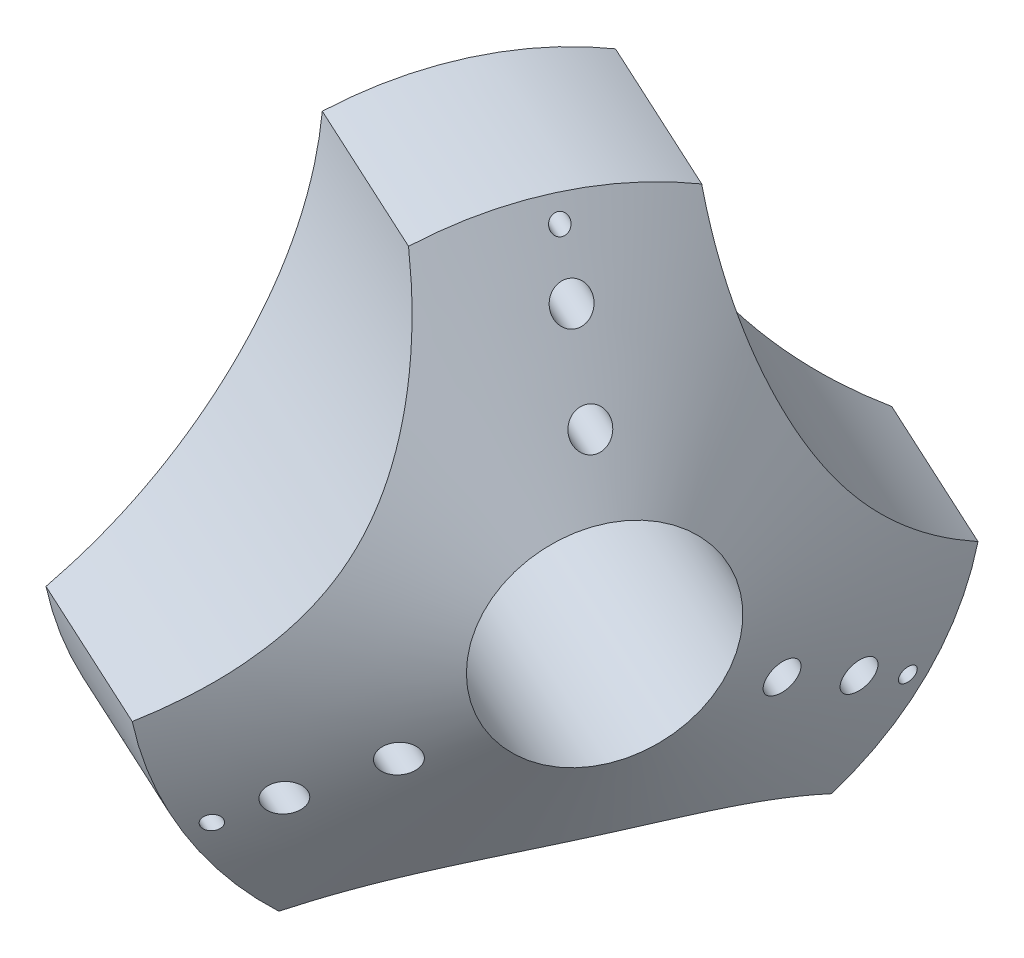
SolidWorks part; units mm, degrees
material "ABS"
ref_plane "前视基准面" through (0, 0, 0) normal (0, 0, 1) x (1, 0, 0)
ref_plane "上视基准面" through (0, 0, 0) normal (0, 1, 0) x (1, 0, 0)
ref_plane "右视基准面" through (0, 0, 0) normal (1, 0, 0) x (0, 0, -1)
other "Configuration Table"
sketch "草图1" plane through (0, 0, 0) normal (0, 1, 0) x (1, 0, 0)
  line L0 (0, 0) -> (50000, 0) construction
  line L1 (0, 0) -> (43301.2702, 25000) construction
  line L2 (0, 0) -> (25000, 43301.2702) construction
  line L3 (0, 0) -> (0, 50000) construction
  line L4 (0, 0) -> (-25000, 43301.2702) construction
  line L5 (0, 0) -> (-43301.2702, 25000) construction
  line L6 (0, -42.1452) -> (-19.2134, -33.2787)
  line L7 (-19.2134, -33.2787) -> (-38.709, -67.046)
  line L8 (-38.709, -67.046) -> (0, -84.9092)
  line L9 (0, -84.9092) -> (0, -42.1452)
  line L10 (-21.968, -74.7716) -> (-17.7779, -65.6918) construction
  line L11 (-17.7779, -65.6918) -> (0, -73.8958)
  line L12 (-17.7779, -65.6918) -> (-33.6882, -58.3496)
  spline S0 degree 4 poles (4.5441, -13.9852) (5.069, -13.9115) (6.1118, -13.7144) (7.5966, -13.2868) (9.4525, -12.4738) (11.1485, -11.4611) (12.673, -10.2854) (14.0902, -8.9027) (15.2006, -7.528) (16.0517, -6.2294) (16.6357, -5.1571) (16.9969, -4.4036) (17.2795, -3.7437) (17.4701, -3.2541) (17.647, -2.7595) (17.7869, -2.3315) (17.8956, -1.9726) (17.9965, -1.6106) (18.0724, -1.3201) (18.1431, -1.0312) (18.201, -0.7763) (18.2495, -0.5466) (18.2961, -0.3139) (18.338, -0.0934) (18.3688, 0.0809) (18.404, 0.2961) (18.438, 0.517) (18.4698, 0.7375) (18.5019, 0.9839) (18.5336, 1.2626) (18.5616, 1.5443) (18.5855, 1.8273) (18.6051, 2.1103) (18.6204, 2.3933) (18.6344, 2.7473) (18.6427, 3.1726) (18.6402, 3.6687) (18.606, 4.6606) (18.4743, 6.0736) (18.1443, 7.891) (17.4882, 10.0676) (16.5951, 12.1579) (15.4804, 14.1385) (14.1536, 15.9992) (12.6297, 17.7192) (10.7951, 19.3989) (8.6272, 20.9716) (6.1287, 22.3558) (3.3088, 23.4722) (0.3713, 24.2251) (-2.6362, 24.611) (-5.6679, 24.6319) (-8.6804, 24.2953) (-11.6337, 23.6131) (-14.4905, 22.6011) (-17.8988, 20.9477) (-21.6682, 18.3857) (-25.4815, 14.66) (-28.8831, 9.6089) (-31.2279, 3.9916) (-32.5355, -2.3024) (-32.5832, -9.4982) (-30.886, -17.2942) (-27.0418, -25.1548) (-21.1423, -32.1629) (-13.78, -37.6027) (-5.394, -41.2569) (3.5764, -43.0207) (12.7127, -42.8868) (21.6333, -40.9289) (30.0036, -37.2857) (37.5425, -32.1439) (44.0239, -25.7248) (49.277, -18.2707) (53.1837, -10.0336) (55.6749, -1.2666) (56.7255, 7.7843) (56.3496, 16.8863) (54.5948, 25.8236) (51.5367, 34.4007) (47.2736, 42.4454) (41.6252, 50.2164) (33.2939, 58.6988) (21.6024, 66.7973) (6.2316, 72.9489) (-11.9297, 75.3897) (-30.1426, 73.5037) (-47.4501, 67.5662) (-63.0493, 58.0235) (-76.3038, 45.4399) (-86.7456, 30.4509) (-94.067, 13.7235) (-98.1075, -4.0757) (-98.837, -22.3066) (-96.337, -40.374) (-90.7813, -57.741) (-82.4178, -73.9383) (-71.5503, -88.568) (-58.5225, -101.306) (-43.7037, -111.9004) (-27.476, -120.169) (-10.2235, -125.9948) (7.6766, -129.3207) (25.8616, -130.1437) (43.989, -128.5088) (59.522, -125.003) (72.4202, -120.5917) (82.8104, -116.0253) (90.8771, -111.8583) (98.6697, -107.1992) (106.1617, -102.071) (114.2246, -95.801) (122.6763, -88.2215) (131.2888, -79.1727) (139.0767, -69.4058) (144.8157, -60.9536) (149.48, -53.1674) (153.2371, -46.1706) (156.1751, -40.0285) (158.8259, -33.7588) (160.8418, -28.4576) (162.3378, -24.1741) (163.5443, -20.3917) (164.5049, -17.1274) (165.2564, -14.393) (165.828, -12.1982) (166.3703, -9.9944) (166.8184, -8.0627) (167.1848, -6.398) (167.4765, -5.0161) (167.7053, -3.8925) (167.892, -2.9476) (168.0629, -2.0497) (168.1956, -1.3461) (168.4043, -0.1916) (168.4882, 0.2863) (168.6688, 1.3366) (168.7622, 1.9047) (168.8711, 2.5704) (169.0198, 3.5044) (169.1948, 4.6573) (169.389, 6.0027) (169.5701, 7.3351) (169.7422, 8.6768) (169.9433, 10.3507) (170.1641, 12.3645) (170.391, 14.7154) (170.6086, 17.4069) (170.7844, 20.1009) (170.9186, 22.7976) (171.0111, 25.4959) (171.0621, 28.1953) (171.0718, 30.8952) (171.0401, 33.595) (170.9491, 36.9686) (170.6302, 43.7113) (169.6923, 53.7988) (167.722, 65.8035) (165.138, 76.2991) (163.208, 82.7681) (162.3863, 85.3398) knots 0 0 0 0 0 0.002183 0.004365 0.006343 0.00832 0.010298 0.012275 0.014479 0.01558 0.016682 0.0173 0.017918 0.018536 0.018845 0.019463 0.019772 0.020081 0.02039 0.020699 0.021008 0.021162 0.021317 0.021626 0.021918 0.022064 0.02221 0.022501 0.022793 0.023085 0.023377 0.023669 0.023961 0.024253 0.024544 0.025128 0.025712 0.026296 0.028631 0.030966 0.033302 0.035637 0.037972 0.040307 0.042695 0.045083 0.048197 0.05131 0.054424 0.057538 0.060652 0.063766 0.066879 0.069993 0.073107 0.07622 0.082448 0.088676 0.094903 0.10113 0.107357 0.114993 0.124334 0.133675 0.143016 0.152357 0.161699 0.17104 0.18038 0.189722 0.199063 0.208404 0.217745 0.227086 0.236427 0.245769 0.25511 0.264451 0.273792 0.283133 0.292474 0.301815 0.313225 0.331907 0.35059 0.369272 0.387954 0.406636 0.425318 0.444001 0.462683 0.481365 0.500047 0.518729 0.537412 0.556094 0.574776 0.593458 0.612141 0.630823 0.649505 0.668187 0.68687 0.705552 0.724234 0.742916 0.752258 0.761599 0.77094 0.780281 0.789622 0.798963 0.812975 0.826987 0.840998 0.85034 0.85501 0.864351 0.873692 0.878363 0.883033 0.887704 0.892374 0.89471 0.897045 0.89938 0.901716 0.904051 0.905219 0.906387 0.907554 0.908722 0.909306 0.90989 0.911057 0.912447 0.912794 0.913142 0.913837 0.915226 0.916616 0.918006 0.919396 0.920785 0.922175 0.924955 0.927734 0.930513 0.933293 0.936072 0.938852 0.941631 0.944411 0.94719 0.94997 0.955529 0.972205 0.988882 1 1 1 1 1 construction
  spline S1 degree 4 poles (18.3541, 0) (18.3651, 0.0621) (18.381, 0.1554) (18.404, 0.2961) (18.438, 0.517) (18.4698, 0.7375) (18.5019, 0.9839) (18.5336, 1.2626) (18.5616, 1.5443) (18.5855, 1.8273) (18.6051, 2.1103) (18.6204, 2.3933) (18.6344, 2.7473) (18.6427, 3.1726) (18.6402, 3.6687) (18.606, 4.6606) (18.4743, 6.0736) (18.1443, 7.891) (17.4882, 10.0676) (16.5951, 12.1579) (15.4804, 14.1385) (14.1536, 15.9992) (12.6297, 17.7192) (10.7951, 19.3989) (8.6272, 20.9716) (6.1287, 22.3558) (3.3088, 23.4722) (0.3713, 24.2251) (-2.6362, 24.611) (-5.6679, 24.6319) (-8.6804, 24.2953) (-11.6337, 23.6131) (-14.4905, 22.6011) (-17.8988, 20.9477) (-21.6682, 18.3857) (-25.4815, 14.66) (-28.8831, 9.6089) (-31.2279, 3.9916) (-32.5355, -2.3024) (-32.5832, -9.4982) (-30.886, -17.2942) (-27.0418, -25.1548) (-21.1423, -32.1629) (-13.78, -37.6027) (-5.394, -41.2569) (3.5764, -43.0207) (12.7127, -42.8868) (21.6333, -40.9289) (30.0036, -37.2857) (37.5425, -32.1439) (44.0239, -25.7248) (49.277, -18.2707) (53.1837, -10.0336) (55.6749, -1.2666) (56.7255, 7.7843) (56.3496, 16.8863) (54.5948, 25.8236) (51.5367, 34.4007) (47.2736, 42.4454) (41.6252, 50.2164) (33.2939, 58.6988) (21.6024, 66.7973) (6.2316, 72.9489) (-11.9297, 75.3897) (-30.1426, 73.5037) (-47.4501, 67.5662) (-63.0493, 58.0235) (-76.3038, 45.4399) (-86.7456, 30.4509) (-94.067, 13.7235) (-98.1075, -4.0757) (-98.837, -22.3066) (-96.337, -40.374) (-90.7813, -57.741) (-82.4178, -73.9383) (-71.5503, -88.568) (-58.5225, -101.306) (-43.7037, -111.9004) (-27.476, -120.169) (-10.2235, -125.9948) (7.6766, -129.3207) (25.8616, -130.1437) (43.989, -128.5088) (59.522, -125.003) (72.4202, -120.5917) (82.8104, -116.0253) (90.8771, -111.8583) (98.6697, -107.1992) (106.1617, -102.071) (114.2246, -95.801) (122.6763, -88.2215) (131.2888, -79.1727) (139.0767, -69.4058) (144.8157, -60.9536) (149.48, -53.1674) (153.2371, -46.1706) (156.1751, -40.0285) (158.8259, -33.7588) (160.8418, -28.4576) (162.3378, -24.1741) (163.5443, -20.3917) (164.5049, -17.1274) (165.2564, -14.393) (165.828, -12.1982) (166.3703, -9.9944) (166.8184, -8.0627) (167.1848, -6.398) (167.4765, -5.0161) (167.7053, -3.8925) (167.892, -2.9476) (168.0629, -2.0497) (168.1956, -1.3461) (168.3264, -0.6223) (168.3933, -0.2484) (168.4372, 0) knots 0.021626 0.021626 0.021626 0.021626 0.021626 0.021918 0.022064 0.02221 0.022501 0.022793 0.023085 0.023377 0.023669 0.023961 0.024253 0.024544 0.025128 0.025712 0.026296 0.028631 0.030966 0.033302 0.035637 0.037972 0.040307 0.042695 0.045083 0.048197 0.05131 0.054424 0.057538 0.060652 0.063766 0.066879 0.069993 0.073107 0.07622 0.082448 0.088676 0.094903 0.10113 0.107357 0.114993 0.124334 0.133675 0.143016 0.152357 0.161699 0.17104 0.18038 0.189722 0.199063 0.208404 0.217745 0.227086 0.236427 0.245769 0.25511 0.264451 0.273792 0.283133 0.292474 0.301815 0.313225 0.331907 0.35059 0.369272 0.387954 0.406636 0.425318 0.444001 0.462683 0.481365 0.500047 0.518729 0.537412 0.556094 0.574776 0.593458 0.612141 0.630823 0.649505 0.668187 0.68687 0.705552 0.724234 0.742916 0.752258 0.761599 0.77094 0.780281 0.789622 0.798963 0.812975 0.826987 0.840998 0.85034 0.85501 0.864351 0.873692 0.878363 0.883033 0.887704 0.892374 0.89471 0.897045 0.89938 0.901716 0.904051 0.905219 0.906387 0.907554 0.908722 0.909306 0.90989 0.911057 0.911057 0.911057 0.911057 0.911057
  spline S2 degree 4 poles (26.7771, -19.4547) (27.2791, -18.9699) (28.2564, -17.9726) (29.6389, -16.3972) (31.5138, -13.8737) (32.9647, -11.4834) (34.0651, -9.2997) (34.8847, -7.3726) (35.3191, -6.2309) (35.6599, -5.2409) (35.9229, -4.4091) (36.0959, -3.8235) (36.2363, -3.3192) (36.3702, -2.8132) (36.4765, -2.3905) (36.5777, -1.9654) (36.6735, -1.5395) (36.7371, -1.2443) (36.7899, -0.9895) (36.8338, -0.7701) (36.8689, -0.5895) (36.9122, -0.3614) (36.9643, -0.079) (37.0022, 0.137) (37.056, 0.4587) (37.1012, 0.7414) (37.1347, 0.96) (37.1737, 1.2255) (37.2176, 1.5413) (37.2661, 1.9157) (37.3168, 2.3441) (37.3624, 2.7721) (37.4134, 3.3079) (37.4649, 3.9519) (37.524, 4.9191) (37.5642, 6.2107) (37.5499, 8.58) (37.2749, 12.0191) (36.4953, 16.2666) (34.9181, 21.2024) (32.7382, 25.9024) (30.2297, 29.9345) (27.5748, 33.3344) (24.3272, 36.7897) (20.4102, 40.1789) (15.3713, 43.5302) (9.113, 46.471) (2.4988, 48.4837) (-3.4771, 49.4179) (-8.6498, 49.6296) (-15.5372, 49.2939) (-22.3494, 48.0444) (-29.7217, 45.4984) (-37.3047, 41.3681) (-42.9225, 37.3494) (-49.2948, 31.5248) (-55.7813, 23.4083) (-61.4472, 12.6507) (-65.4181, -1.9048) (-66.0143, -20.496) (-61.2011, -38.6277) (-51.6663, -54.6681) (-39.5267, -67.0168) (-28.241, -75.0457) (-15.7631, -81.0448) (-2.4709, -84.9081) (11.2641, -86.5959) (25.0917, -86.1269) (38.6859, -83.5703) (51.7521, -79.0376) (62.4941, -73.4702) (71.0671, -67.6624) (77.7289, -62.1925) (82.7475, -57.4634) (87.4361, -52.4071) (91.7776, -47.05) (95.7571, -41.4188) (99.3618, -35.5409) (102.1786, -30.2056) (104.3465, -25.5122) (105.8226, -21.9278) (106.7439, -19.5134) (107.4694, -17.486) (108.0246, -15.8552) (108.5543, -14.216) (109.0585, -12.5687) (109.5372, -10.914) (109.9904, -9.2519) (110.418, -7.5833) (110.7697, -6.1172) (111.0551, -4.8577) (111.2824, -3.8044) (111.4574, -2.9629) (111.6056, -2.2213) (111.7181, -1.6396) (111.7961, -1.2276) (111.8764, -0.7956) (111.9824, -0.2107) (112.0406, 0.1173) (112.149, 0.7476) (112.2197, 1.1704) (112.2736, 1.499) (112.3401, 1.912) (112.4454, 2.5814) (112.5829, 3.4978) (112.7468, 4.6683) (112.9181, 6.007) (113.1127, 7.6834) (113.3147, 9.6981) (113.5046, 12.0531) (113.6588, 14.7487) (113.7504, 17.4473) (113.7796, 20.1472) (113.7303, 24.197) (113.4243, 30.2662) (112.8255, 35.6383) (112.057, 40.3021) (111.5392, 42.9519) knots 0 0 0 0 0 0.005611 0.011222 0.016833 0.02525 0.028055 0.030861 0.033666 0.035069 0.036472 0.037875 0.038576 0.039277 0.04068 0.041381 0.042083 0.042784 0.043135 0.043486 0.043836 0.044187 0.044888 0.045754 0.046187 0.04662 0.047052 0.047485 0.048351 0.049216 0.050082 0.050948 0.051813 0.053545 0.055276 0.058738 0.062201 0.072588 0.082976 0.093363 0.103751 0.114138 0.121063 0.127988 0.141838 0.155688 0.169538 0.183388 0.197238 0.204163 0.211088 0.238788 0.252638 0.266488 0.280339 0.294189 0.321888 0.349589 0.377289 0.414571 0.469971 0.497671 0.525371 0.553071 0.580771 0.608471 0.636171 0.663871 0.691571 0.719271 0.746971 0.760821 0.774671 0.788521 0.802371 0.816222 0.830072 0.843922 0.857772 0.864697 0.871622 0.875084 0.878547 0.882009 0.885472 0.888934 0.892397 0.895859 0.899322 0.902784 0.904515 0.906247 0.907978 0.909709 0.910575 0.911008 0.91144 0.913172 0.914528 0.915207 0.915885 0.916563 0.917242 0.918599 0.921312 0.924025 0.926739 0.929452 0.934879 0.940306 0.945732 0.951159 0.956586 0.962013 0.978293 1 1 1 1 1 construction
  spline S3 degree 4 poles (36.9778, 0) (36.994, 0.0921) (37.0177, 0.2297) (37.056, 0.4587) (37.1012, 0.7414) (37.1347, 0.96) (37.1737, 1.2255) (37.2176, 1.5413) (37.2661, 1.9157) (37.3168, 2.3441) (37.3624, 2.7721) (37.4134, 3.3079) (37.4649, 3.9519) (37.524, 4.9191) (37.5642, 6.2107) (37.5499, 8.58) (37.2749, 12.0191) (36.4953, 16.2666) (34.9181, 21.2024) (32.7382, 25.9024) (30.2297, 29.9345) (27.5748, 33.3344) (24.3272, 36.7897) (20.4102, 40.1789) (15.3713, 43.5302) (9.113, 46.471) (2.4988, 48.4837) (-3.4771, 49.4179) (-8.6498, 49.6296) (-15.5372, 49.2939) (-22.3494, 48.0444) (-29.7217, 45.4984) (-37.3047, 41.3681) (-42.9225, 37.3494) (-49.2948, 31.5248) (-55.7813, 23.4083) (-61.4472, 12.6507) (-65.4181, -1.9048) (-66.0143, -20.496) (-61.2011, -38.6277) (-51.6663, -54.6681) (-39.5267, -67.0168) (-28.241, -75.0457) (-15.7631, -81.0448) (-2.4709, -84.9081) (11.2641, -86.5959) (25.0917, -86.1269) (38.6859, -83.5703) (51.7521, -79.0376) (62.4941, -73.4702) (71.0671, -67.6624) (77.7289, -62.1925) (82.7475, -57.4634) (87.4361, -52.4071) (91.7776, -47.05) (95.7571, -41.4188) (99.3618, -35.5409) (102.1786, -30.2056) (104.3465, -25.5122) (105.8226, -21.9278) (106.7439, -19.5134) (107.4694, -17.486) (108.0246, -15.8552) (108.5543, -14.216) (109.0585, -12.5687) (109.5372, -10.914) (109.9904, -9.2519) (110.418, -7.5833) (110.7697, -6.1172) (111.0551, -4.8577) (111.2824, -3.8044) (111.4574, -2.9629) (111.6056, -2.2213) (111.7181, -1.6396) (111.7961, -1.2276) (111.8764, -0.7956) (111.946, -0.4114) (111.9868, -0.1841) (112.0193, 0) knots 0.044888 0.044888 0.044888 0.044888 0.044888 0.045754 0.046187 0.04662 0.047052 0.047485 0.048351 0.049216 0.050082 0.050948 0.051813 0.053545 0.055276 0.058738 0.062201 0.072588 0.082976 0.093363 0.103751 0.114138 0.121063 0.127988 0.141838 0.155688 0.169538 0.183388 0.197238 0.204163 0.211088 0.238788 0.252638 0.266488 0.280339 0.294189 0.321888 0.349589 0.377289 0.414571 0.469971 0.497671 0.525371 0.553071 0.580771 0.608471 0.636171 0.663871 0.691571 0.719271 0.746971 0.760821 0.774671 0.788521 0.802371 0.816222 0.830072 0.843922 0.857772 0.864697 0.871622 0.875084 0.878547 0.882009 0.885472 0.888934 0.892397 0.895859 0.899322 0.902784 0.904515 0.906247 0.907978 0.909709 0.910575 0.911008 0.91144 0.913172 0.913172 0.913172 0.913172 0.913172
  dimension "D1" = 10
revolve "旋转1" add sketch "草图1" angle 360 about L8 region at (-9.8708, 0, 38.2044) region at (-13.644, 0, 53.5737)
ref_plane "基准面1" through (-5.5743, 0, -2.5724) normal (-0.908, 0, -0.419) x (-0.419, 0, 0.908)
sketch "草图2" plane through (-5.5743, 0, -2.5724) normal (-0.908, 0, -0.419) x (-0.419, 0, 0.908)
  line L0 (77.096, 38.829) -> (77.096, 36.329)
  line L1 (77.096, 0) -> (77.096, 20) construction
  line L2 (77.096, 20) -> (77.096, 30)
  line L3 (77.096, 0) -> (9.8925, 38.8) construction
  circle A0 centre (77.096, 0) radius 38.829 construction
  circle A1 centre (77.096, 36.329) radius 1
  circle A2 centre (77.096, 30) radius 2
  circle A3 centre (77.096, 20) radius 2
  circle A4 centre (9.8925, 38.8) radius 54
  circle A5 centre (144.2996, 38.8) radius 54
  circle A6 centre (108.5579, -18.1645) radius 1
  circle A7 centre (103.0768, -15) radius 2
  circle A8 centre (94.4165, -10) radius 2
  circle A9 centre (77.096, -77.6) radius 54
  circle A10 centre (45.6342, -18.1645) radius 1
  circle A11 centre (51.1153, -15) radius 2
  circle A12 centre (59.7755, -10) radius 2
  circle A13 centre (77.096, 0) radius 12.5
  point P0 (77.096, 0)
  dimension "D4" = 2
  dimension "D5" = 4
  dimension "D6" = 4
  dimension "D8" = 108
  dimension "D10" = 25
  dimension "D1" = 2.5
  dimension "D2" = 20
  dimension "D3" = 10
  dimension "D7" = 60
  dimension "D9" = 3
extrude "切除-拉伸1" cut sketch "草图2" against normal blind 58 contours A4 | A5 | A9 | A1 | A2 | L1 A3 L2 | L2 A3 L1 | A6 | A7 | A8 | A12 | A11 | A10 | A13 region at (-37.3024, 31.3742, 66.1817) region at (-38.4541, 21.3742, 68.6772) region at (-37.5903, 35.6419, 66.8055) region at (-9.7193, 38.8, 6.4098) region at (-66.0372, 38.8, 128.4491) region at (-51.061, -18.1645, 95.9962) region at (-48.7644, -15, 91.0195) region at (-45.1357, -10, 83.1561) region at (-37.8783, -77.6, 67.4294) region at (-24.6955, -18.1645, 38.8626) region at (-26.9921, -15, 43.8394) region at (-30.6208, -10, 51.7027) region at (-37.8783, 0, 67.4294)
fillet "圆角1" radius 3.5 1 edges at (-32.4329, 0, 56.1755)
shell "抽壳1" thickness 2
